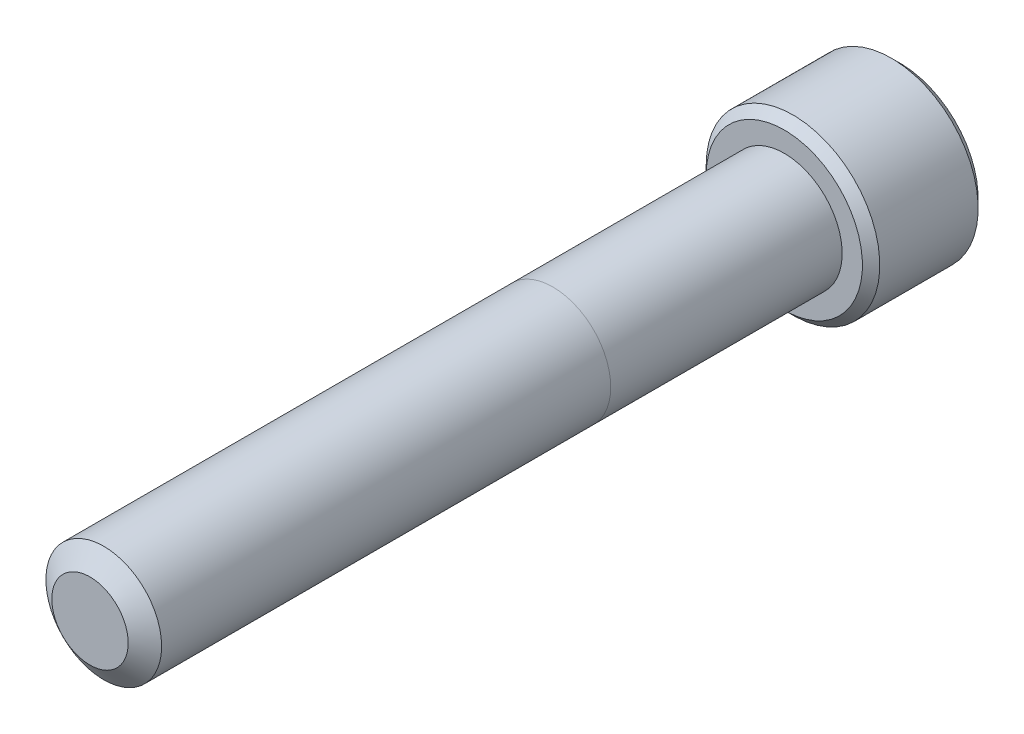
SolidWorks part; units mm, degrees
ref_plane "Front Plane" through (0, 0, 0) normal (0, 0, 1) x (1, 0, 0)
ref_plane "Top Plane" through (0, 0, 0) normal (0, 1, 0) x (1, 0, 0)
ref_plane "Right Plane" through (0, 0, 0) normal (1, 0, 0) x (0, 0, -1)
sketch "Sketch1" plane through (0, 0, 0) normal (0, 0, 1) x (1, 0, 0)
  circle A0 centre (0, 0) radius 3.175
  dimension "OD" = 6.35
extrude "Extrude1" add sketch "Sketch1" against normal blind 38.1
sketch "Sketch2" plane through (0, 0, 0) normal (0, 0, 1) x (1, 0, 0)
  circle A0 centre (0, 0) radius 3.175 construction
  circle A1 centre (0, 0) radius 3.175
curve "Helix/Spiral1" [suppressed] pitch 1.27 height 39.37 turns 31 parameters "pitch"=1.27
sketch "Sketch3" plane through (0, 0, 0) normal (1, 0, 0) x (0, 0, -1)
  line L0 (-1.1113, 3.175) -> (-0.635, 2.3501)
  line L1 (-0.635, 2.3501) -> (-0.4763, 2.3501)
  line L2 (-0.4763, 2.3501) -> (0, 3.175)
  line L3 (-1.1113, 3.175) -> (0, 3.175)
  line L4 (-0.5556, 3.175) -> (-0.5556, 2.3501) construction
  line L5 (-0.8731, 2.7626) -> (-0.2381, 2.7626) construction
  line L6 (0, 3.175) -> (0, -3.175) construction
  dimension "D1" = 0.1588
  dimension "D2" = 0.635
  dimension "D3" = 60
sweep "Cut-Sweep1" [suppressed] cut profiles "Sketch3" path "Helix/Spiral1"
sketch "Sketch4" plane through (0, 0, 0) normal (1, 0, 0) x (0, 0, -1)
  line L0 (0.7554, 3.175) -> (0, 2.0961)
  line L1 (0, 2.0961) -> (0, 3.175)
  line L2 (0.7554, 3.175) -> (0, 3.175)
  line L3 (-1.1113, 3.175) -> (0, 3.175) construction
  line L4 (0, 0) -> (7.0209, 0) construction
  dimension "D1" = 55
  dimension "D2" = 0.254
revolve "Cut-Revolve1" cut sketch "Sketch4" angle 360 about L4
sketch "Sketch5" [suppressed] plane through (0, 0, 0) normal (1, 0, 0) x (0, 0, -1)
  line L0 (38.1, -2.3728) -> (38.1, 2.2654) construction
  line L1 (38.1, 3.302) -> (25.5202, 3.302)
  line L2 (38.1, 3.302) -> (38.1, 0)
  line L3 (38.1, 0) -> (25.4, 0)
  line L4 (25.4, 2.9718) -> (25.4, 0)
  line L5 (25.5202, 3.302) -> (25.4, 2.9718)
  line L6 (0, 0) -> (9.9695, 0) construction
  point P3 (25.4, 3.302)
  point P10 (25.4, 3.302)
  dimension "D1" = 0.3302
  dimension "Thread min" = 25.4
  dimension "D2" = 0.127
  dimension "D3" = 20
revolve "partially thread" [suppressed] add sketch "Sketch5" angle 360 about L6
sketch "Sketch6" plane through (0, 0, -38.1) normal (0, 0, -1) x (-1, 0, 0)
  circle A0 centre (0, 0) radius 4.7625
  dimension "head dia" = 9.525
extrude "Extrude2" add sketch "Sketch6" along normal blind 6.35
sketch "Sketch7" plane through (0, 0, -44.45) normal (0, 0, -1) x (-1, 0, 0)
  line L1 (0, 2.7496) -> (-2.3812, 1.3748)
  line L2 (-2.3812, 1.3748) -> (-2.3813, -1.3748)
  line L3 (-2.3813, -1.3748) -> (0, -2.7496)
  line L4 (0, -2.7496) -> (2.3812, -1.3748)
  line L5 (2.3812, -1.3748) -> (2.3812, 1.3748)
  line L6 (2.3812, 1.3748) -> (0, 2.7496)
  circle A0 centre (0, 0) radius 2.3813 construction
  dimension "hex dia" = 4.7625
extrude "Cut-Extrude1" cut sketch "Sketch7" against normal blind 3.5719
sketch "Sketch8" plane through (0, 0, -44.45) normal (0, 0, -1) x (-1, 0, 0)
  circle A0 centre (0, 0) radius 2.7496
extrude "Cut-Extrude2" cut sketch "Sketch8" against normal through all draft 45
chamfer "Chamfer1" distance 0.4763 angle 45 2 edges at (-4.7625, 0, -44.45) (-4.7625, 0, -38.1)
sketch "Sketch9" plane through (0, 0, 0) normal (1, 0, 0) x (0, 0, -1)
  line L0 (0, 3.175) -> (0, -3.175) construction
  line L1 (6.985, 3.175) -> (6.985, -3.175) construction
  dimension "D1" = 6.985
sketch "Sketch10" plane through (0, 0, 0) normal (0, 1, 0) x (1, 0, 0)
  line L0 (-3.175, 25.4) -> (3.175, 25.4)
  line L1 (-3.175, 38.1) -> (-3.175, 0.7554) construction
  line L2 (3.175, 0.7554) -> (3.175, 38.1) construction
  line L3 (-2.0961, 0) -> (2.0961, 0) construction
  dimension "D1" = 25.4
split line "Split Line3"
equation "\"D3@Helix/Spiral1\" = \"screw length@Extrude1\"+\"pitch@Helix/Spiral1\""
equation "\"D1@Sketch3\" = \"pitch@Helix/Spiral1\"*.125"
equation "\"D2@Sketch3\" = \"pitch@Helix/Spiral1\"*.5"
equation "\"D1@Cut-Extrude1\" = \"hex dia@Sketch7\"*.75"
equation "\"D1@Chamfer1\" = \"head dia@Sketch6\"*.05"
equation "\"D1@Sketch9\" = \"pitch@Helix/Spiral1\"*5.5"
